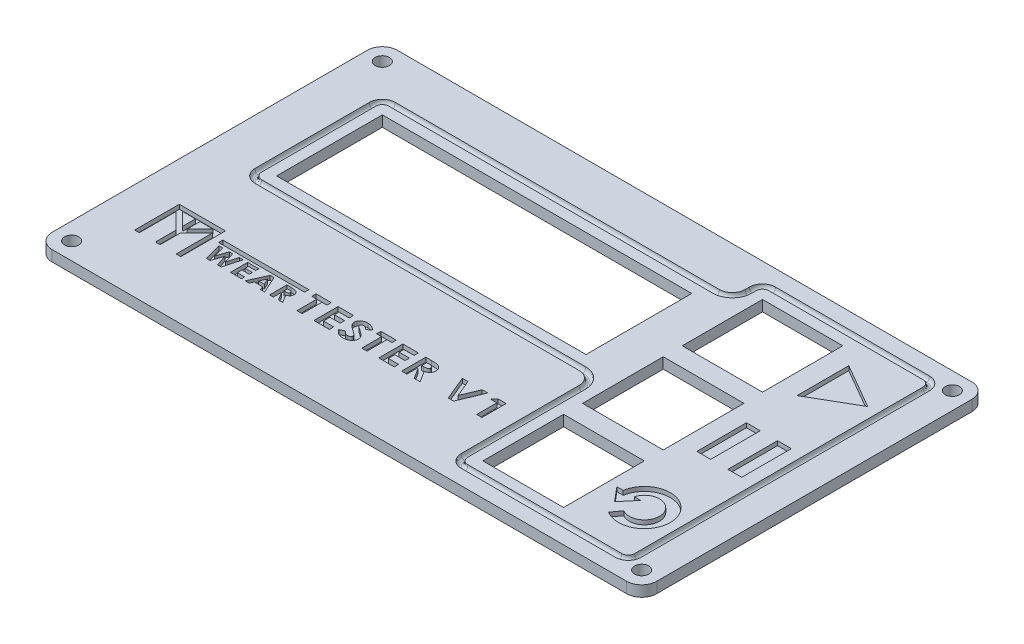
SolidWorks part; units mm, degrees
material "PET"
ref_plane "Front Plane" through (0, 0, 0) normal (0, 0, 1) x (1, 0, 0)
ref_plane "Top Plane" through (0, 0, 0) normal (0, 1, 0) x (1, 0, 0)
ref_plane "Right Plane" through (0, 0, 0) normal (1, 0, 0) x (0, 0, -1)
sketch "Sketch1" plane through (0, 0, 0) normal (0, 1, 0) x (1, 0, 0)
  line L0 (26.05, -9.1) -> (44.15, -9.1)
  line L1 (-55.05, 25) -> (16.05, 25) construction
  line L2 (-55.05, 25) -> (-55.05, 1.1) construction
  line L3 (-55.05, 1.1) -> (16.05, 1.1) construction
  line L4 (16.05, 25) -> (16.05, 1.1) construction
  line L5 (26.05, 14) -> (44.05, 14)
  line L6 (26.05, 14) -> (26.05, 32)
  line L7 (26.05, 32) -> (44.05, 32)
  line L8 (44.05, 14) -> (44.05, 32)
  line L9 (26.05, 14) -> (44.05, 32) construction
  line L10 (26.05, 32) -> (44.05, 14) construction
  line L11 (26.05, -9.1) -> (26.05, 9)
  line L12 (26.05, 9) -> (44.15, 9)
  line L13 (44.15, -9.1) -> (44.15, 9)
  line L14 (26.05, -9.1) -> (44.15, 9) construction
  line L15 (26.05, 9) -> (44.15, -9.1) construction
  line L16 (26.05, -32.2) -> (44.15, -32.2)
  line L17 (26.05, -32.2) -> (26.05, -14.1)
  line L18 (26.05, -14.1) -> (44.15, -14.1)
  line L19 (44.15, -32.2) -> (44.15, -14.1)
  line L20 (26.05, -32.2) -> (44.15, -14.1) construction
  line L21 (26.05, -14.1) -> (44.15, -32.2) construction
  line L22 (47.05, -9) -> (65.05, -9)
  line L23 (47.05, 14) -> (65.05, 14)
  line L24 (47.05, 14) -> (47.05, 32)
  line L25 (47.05, 32) -> (65.05, 32)
  line L26 (65.05, 14) -> (65.05, 32)
  line L27 (47.05, 14) -> (65.05, 32) construction
  line L28 (47.05, 32) -> (65.05, 14) construction
  line L29 (47.05, -9) -> (47.05, 9)
  line L30 (47.05, 9) -> (65.05, 9)
  line L31 (65.05, -9) -> (65.05, 9)
  line L32 (47.05, -9) -> (65.05, 9) construction
  line L33 (47.05, 9) -> (65.05, -9) construction
  line L34 (47.05, -32.1) -> (65.05, -32.1)
  line L35 (47.05, -32.1) -> (47.05, -14.1)
  line L36 (47.05, -14.1) -> (65.05, -14.1)
  line L37 (65.05, -32.1) -> (65.05, -14.1)
  line L38 (47.05, -32.1) -> (65.05, -14.1) construction
  line L39 (47.05, -14.1) -> (65.05, -32.1) construction
  line L40 (-55.35, 25.3) -> (16.35, 25.3)
  line L41 (-70.05, -40) -> (70.05, -40)
  line L42 (-70.05, -40) -> (-70.05, 40)
  line L43 (-70.05, 40) -> (70.05, 40)
  line L44 (70.05, -40) -> (70.05, 40)
  line L45 (-70.05, -40) -> (70.05, 40) construction
  line L46 (-70.05, 40) -> (70.05, -40) construction
  line L48 (-70.05, 0) -> (70.05, 0) construction
  line L50 (16.05, -25) -> (16.05, -1.1) construction
  line L51 (-55.05, -25) -> (16.05, -25) construction
  line L52 (-55.05, -25) -> (-55.05, -1.1) construction
  line L53 (-55.05, -1.1) -> (16.05, -1.1) construction
  line L55 (-59.45, 32.1) -> (20.55, 32.1) construction
  line L56 (-59.45, 32.1) -> (-59.45, -3.9) construction
  line L57 (-59.45, -3.9) -> (20.55, -3.9) construction
  line L58 (20.55, 32.1) -> (20.55, -3.9) construction
  line L60 (16.35, 25.3) -> (16.35, 0.8)
  line L61 (-55.35, 0.8) -> (16.35, 0.8)
  line L62 (-55.35, 25.3) -> (-55.35, 0.8)
  line L63 (25.75, 32.3) -> (44.35, 32.3)
  line L64 (44.35, 13.7) -> (44.35, 32.3)
  line L65 (25.75, 13.7) -> (44.35, 13.7)
  line L66 (25.75, 13.7) -> (25.75, 32.3)
  line L67 (25.75, 9.3) -> (44.45, 9.3)
  line L68 (44.45, -9.4) -> (44.45, 9.3)
  line L69 (25.75, -9.4) -> (44.45, -9.4)
  line L70 (25.75, -9.4) -> (25.75, 9.3)
  line L71 (25.75, -13.8) -> (44.45, -13.8)
  line L72 (44.45, -32.5) -> (44.45, -13.8)
  line L73 (25.75, -32.5) -> (44.45, -32.5)
  line L74 (25.75, -32.5) -> (25.75, -13.8)
  line L76 (-66.05, -36) -> (66.05, -36) construction
  line L77 (-66.05, -36) -> (-66.05, 36) construction
  line L78 (-66.05, 36) -> (66.05, 36) construction
  line L79 (66.05, -36) -> (66.05, 36) construction
  line L80 (-66.05, -36) -> (66.05, 36) construction
  line L81 (-66.05, 36) -> (66.05, -36) construction
  line L82 (-70.05, 40) -> (-85.05, 40)
  line L83 (-70.05, 40) -> (-70.05, -40)
  line L84 (-70.05, -40) -> (-85.05, -40)
  line L85 (-85.05, 40) -> (-85.05, -40)
  circle A0 centre (-66.05, 36) radius 1.65
  circle A1 centre (-66.05, -36) radius 1.65
  circle A2 centre (66.05, -36) radius 1.65
  circle A3 centre (66.05, 36) radius 1.65
  point P4 (35.05, 23)
  point P10 (35.1, -0.05)
  point P15 (35.1, -23.15)
  point P20 (56.05, 23)
  point P25 (56.05, 0)
  point P30 (56.05, -23.1)
  point P35 (0, 0)
  point P66 (0, 0)
  dimension "D25" = 3.3
  dimension "D1" = 71.1
  dimension "D2" = 23.9
  dimension "D3" = 18
  dimension "D4" = 18.1
  dimension "D5" = 18.1
  dimension "D6" = 18
  dimension "D7" = 18
  dimension "D8" = 18
  dimension "D9" = 5
  dimension "D10" = 5
  dimension "D11" = 3
  dimension "D12" = 8
  dimension "D13" = 80
  dimension "D15" = 10
  dimension "D16" = 15
  dimension "D17" = 15
  dimension "D18" = 5
  dimension "D19" = 36
  dimension "D20" = 80
  dimension "D21" = 5
  dimension "D22" = 4.5
  dimension "D26" = 4
  dimension "D24" = 4
  dimension "D27" = 15
  dimension "D14" = 0.3
  dimension "D23" = 0.3
extrude "Boss-Extrude1" add sketch "Sketch1" along normal blind 2.5 contours L41 L44 L43 L42 L69 L70 L67 L68 L37 L34 L35 L36 L31 L22 L29 L30 L26 L23 L24 L25 L62 L40 L60 L61 L65 L66 L63 L64 L73 L74 L71 L72 | L22 L31 L30 L29 | L23 L26 L25 L24 | L34 L37 L36 L35 region at (56.05, 0, 0) region at (56.05, 0, -23) region at (56.05, 0, 23.1) region at (-7.6894, 0, 3.0725)
fillet "Fillet1" radius 3.5 4 edges at (-70.05, 1.25, 40) (70.05, 1.25, 40) (70.05, 1.25, -40) (-70.05, 1.25, -40)
sketch "Sketch2" plane through (0, 2.5, 0) normal (0, 1, 0) x (1, 0, 0)
  line L0 (49.0427, 29) -> (49.0427, 17)
  line L1 (49.0427, 17) -> (59.435, 23)
  line L2 (59.435, 23) -> (49.0427, 29)
  line L3 (55.836, 5.7) -> (59.036, 5.7)
  line L4 (48.636, 5.7) -> (51.836, 5.7)
  line L5 (48.636, 5.7) -> (48.636, -5.8)
  line L6 (48.636, -5.8) -> (51.836, -5.8)
  line L7 (51.836, 5.7) -> (51.836, -5.8)
  line L8 (55.836, 5.7) -> (55.836, -5.8)
  line L9 (55.836, -5.8) -> (59.036, -5.8)
  line L10 (59.036, 5.7) -> (59.036, -5.8)
  line L11 (59.435, 23) -> (52.1492, 23) construction
  line L12 (59.036, -0.05) -> (48.636, -0.05) construction
  line L13 (53.836, 32.2951) -> (53.836, -34.6108) construction
  line L14 (49.2009, -25.4273) -> (46.4509, -22.15)
  line L15 (46.4509, -22.15) -> (47.9199, -22.15)
  line L16 (51.9509, -22.15) -> (49.2009, -25.4273)
  line L17 (57.0474, -22.15) -> (62.8011, -22.15) construction
  line L18 (50.4819, -22.15) -> (51.9509, -22.15)
  line L19 (50.6084, -28.2079) -> (52.085, -26.1805)
  line L20 (25.75, 23) -> (83.5755, 23) construction
  line L21 (25.75, 13.7) -> (25.75, 32.3) construction
  line L22 (25.75, -0.05) -> (86.018, -0.05) construction
  line L23 (25.75, -9.4) -> (25.75, 9.3) construction
  line L24 (25.75, -23.15) -> (93.8874, -23.15) construction
  line L25 (25.75, -32.5) -> (25.75, -13.8) construction
  line L26 (-63.1758, 72.6469) -> (86.8242, 72.6469) construction
  line L31 (-59.35, -0.2) -> (-59.35, 26.3)
  line L32 (-56.35, 29.3) -> (18.75, 29.3)
  line L33 (21.75, 32.3) -> (21.75, 33.3)
  line L34 (24.75, 36.3) -> (60.435, 36.3)
  line L35 (63.435, 33.3) -> (63.435, -33.5)
  line L36 (60.435, -36.5) -> (24.75, -36.5)
  line L37 (21.75, -33.5) -> (21.75, -6.2)
  line L38 (18.75, -3.2) -> (-56.35, -3.2)
  line L39 (-55.35, 25.3) -> (-55.35, 0.8) construction
  line L40 (-55.35, 0.8) -> (16.35, 0.8) construction
  line L41 (-55.5842, -5.7958) -> (-55.5842, -42.6703) construction
  line L42 (-55.35, 25.3) -> (16.35, 25.3) construction
  line L43 (25.75, 32.3) -> (44.35, 32.3) construction
  line L44 (25.75, -32.5) -> (44.45, -32.5) construction
  line L45 (-56.35, 27.8) -> (18.75, 27.8)
  line L46 (23.25, 32.3) -> (23.25, 33.3)
  line L47 (24.75, 34.8) -> (60.435, 34.8)
  line L48 (61.935, 33.3) -> (61.935, -33.5)
  line L49 (60.435, -35) -> (24.75, -35)
  line L50 (23.25, -33.5) -> (23.25, -6.2)
  line L51 (18.75, -1.7) -> (-56.35, -1.7)
  line L52 (-57.85, -0.2) -> (-57.85, 26.3)
  line L53 (-60.9283, -26.5177) -> (-60.9283, -16.1677)
  line L54 (-60.9283, -16.1677) -> (-50.24, -16.1677)
  line L55 (-60.9283, -26.5177) -> (-59.8499, -26.5177)
  line L56 (-59.8499, -26.5177) -> (-59.8499, -18.0492)
  line L57 (-59.8499, -18.0492) -> (-56.1242, -21.7607)
  line L58 (-56.1242, -21.7607) -> (-56.1242, -26.5177)
  line L59 (-56.1242, -26.5177) -> (-55.0442, -26.5177)
  line L60 (-59.1242, -17.2477) -> (-56.1242, -17.2477)
  line L61 (-56.1242, -17.2477) -> (-56.1242, -20.2363)
  line L62 (-56.1242, -20.2363) -> (-59.1242, -17.2477)
  line L63 (-55.0442, -20.2363) -> (-52.0442, -17.2477)
  line L64 (-55.0442, -17.2477) -> (-55.0442, -20.2363)
  line L65 (-52.0442, -17.2477) -> (-55.0442, -17.2477)
  line L66 (-55.0442, -21.7607) -> (-55.0442, -26.5177)
  line L67 (-51.3184, -18.0492) -> (-55.0442, -21.7607)
  line L68 (-51.3184, -26.5177) -> (-51.3184, -18.0492)
  line L69 (-50.24, -26.5177) -> (-51.3184, -26.5177)
  line L70 (-50.24, -26.5177) -> (-50.24, -16.1677)
  line L71 (-50.24, -16.1677) -> (15.8679, -16.1677) construction
  line L72 (-50.24, -26.5177) -> (17.2285, -26.5177) construction
  line L73 (-23.65, -6.2) -> (-23.65, -36) construction
  line L74 (-66.05, -6.2) -> (18.75, -6.2) construction
  line L75 (-66.05, -6.2) -> (-66.05, -36) construction
  line L76 (-66.05, -36) -> (18.75, -36) construction
  line L77 (18.75, -6.2) -> (18.75, -36) construction
  line L78 (-66.05, -21.1) -> (18.75, -21.1) construction
  line L79 (-48.2019, -23.9) -> (-29.2655, -23.9) construction
  line L80 (-48.7019, -18.3) -> (-28.7655, -18.3)
  line L81 (-48.7019, -18.3) -> (-48.7019, -19.3)
  line L82 (-48.7019, -19.3) -> (-28.7655, -19.3)
  line L83 (-28.7655, -18.3) -> (-28.7655, -19.3)
  line L84 (-48.2019, -18.3) -> (-29.2655, -18.3) construction
  line L85 (-27.241, -23.9) -> (18.0219, -23.9) construction
  line L86 (-48.0224, -19.9) -> (-47.1258, -19.9)
  line L87 (-47.1258, -19.9) -> (-46.4327, -22.4537)
  line L88 (-46.4327, -22.4537) -> (-45.5793, -19.9)
  line L89 (-45.5793, -19.9) -> (-44.8213, -19.9)
  line L90 (-44.8213, -19.9) -> (-43.9711, -22.4537)
  line L91 (-43.9711, -22.4537) -> (-43.2796, -19.9)
  line L92 (-43.2796, -19.9) -> (-42.3814, -19.9)
  line L93 (-42.3814, -19.9) -> (-43.4655, -23.9)
  line L94 (-43.4655, -23.9) -> (-44.3405, -23.9)
  line L95 (-44.3405, -23.9) -> (-45.2019, -21.3143)
  line L96 (-45.2019, -21.3143) -> (-46.0657, -23.9)
  line L97 (-46.0657, -23.9) -> (-46.9359, -23.9)
  line L98 (-46.9359, -23.9) -> (-48.0224, -19.9)
  line L99 (-41.3404, -19.9) -> (-38.7763, -19.9)
  line L100 (-38.7763, -19.9) -> (-38.7763, -20.6179)
  line L101 (-38.7763, -20.6179) -> (-40.4686, -20.6179)
  line L102 (-40.4686, -20.6179) -> (-40.4686, -21.3872)
  line L103 (-40.4686, -21.3872) -> (-38.7763, -21.3872)
  line L104 (-38.7763, -21.3872) -> (-38.7763, -22.1051)
  line L105 (-38.7763, -22.1051) -> (-40.4686, -22.1051)
  line L106 (-40.4686, -22.1051) -> (-40.4686, -23.1821)
  line L107 (-40.4686, -23.1821) -> (-38.7763, -23.1821)
  line L108 (-38.7763, -23.1821) -> (-38.7763, -23.9)
  line L109 (-38.7763, -23.9) -> (-41.3404, -23.9)
  line L110 (-41.3404, -23.9) -> (-41.3404, -19.9)
  line L111 (-36.1319, -19.9) -> (-35.2376, -19.9)
  line L112 (-35.2376, -19.9) -> (-33.4275, -23.9)
  line L113 (-33.4275, -23.9) -> (-34.3594, -23.9)
  line L114 (-34.3594, -23.9) -> (-34.7232, -23.0795)
  line L115 (-34.7232, -23.0795) -> (-36.6439, -23.0795)
  line L116 (-36.6439, -23.0795) -> (-37.0077, -23.9)
  line L117 (-37.0077, -23.9) -> (-37.9404, -23.9)
  line L118 (-37.9404, -23.9) -> (-36.1319, -19.9)
  line L119 (-35.6839, -20.9729) -> (-36.3266, -22.3615)
  line L120 (-36.3266, -22.3615) -> (-35.0413, -22.3615)
  line L121 (-35.0413, -22.3615) -> (-35.6839, -20.9729)
  line L122 (-32.2839, -19.9) -> (-31.3256, -19.9)
  line L123 (-30.3617, -22.0747) -> (-29.2327, -23.9)
  line L124 (-29.2327, -23.9) -> (-30.2158, -23.9)
  line L125 (-30.2158, -23.9) -> (-31.2944, -22.1564)
  line L126 (-31.2944, -22.1564) -> (-31.4121, -22.1564)
  line L127 (-31.4121, -22.1564) -> (-31.4121, -23.9)
  line L128 (-31.4121, -23.9) -> (-32.2839, -23.9)
  line L129 (-32.2839, -23.9) -> (-32.2839, -19.9)
  line L130 (-31.4121, -21.4385) -> (-31.1189, -21.4385)
  line L131 (-31.1557, -20.6179) -> (-31.4121, -20.6179)
  line L132 (-31.4121, -20.6179) -> (-31.4121, -21.4385)
  line L133 (-27.0974, -18.3) -> (-23.5794, -18.3)
  line L134 (-23.5794, -18.3) -> (-23.5794, -19.3051)
  line L135 (-23.5794, -19.3051) -> (-24.7281, -19.3051)
  line L136 (-24.7281, -19.3051) -> (-24.7281, -23.9)
  line L137 (-24.7281, -23.9) -> (-25.9487, -23.9)
  line L138 (-25.9487, -23.9) -> (-25.9487, -19.3051)
  line L139 (-25.9487, -19.3051) -> (-27.0974, -19.3051)
  line L140 (-27.0974, -19.3051) -> (-27.0974, -18.3)
  line L141 (-22.0143, -18.3) -> (-18.4246, -18.3)
  line L142 (-18.4246, -18.3) -> (-18.4246, -19.3051)
  line L143 (-18.4246, -19.3051) -> (-20.7938, -19.3051)
  line L144 (-20.7938, -19.3051) -> (-20.7938, -20.3821)
  line L145 (-20.7938, -20.3821) -> (-18.4246, -20.3821)
  line L146 (-18.4246, -20.3821) -> (-18.4246, -21.3872)
  line L147 (-18.4246, -21.3872) -> (-20.7938, -21.3872)
  line L148 (-20.7938, -21.3872) -> (-20.7938, -22.8949)
  line L149 (-20.7938, -22.8949) -> (-18.4246, -22.8949)
  line L150 (-18.4246, -22.8949) -> (-18.4246, -23.9)
  line L151 (-18.4246, -23.9) -> (-22.0143, -23.9)
  line L152 (-22.0143, -23.9) -> (-22.0143, -18.3)
  line L153 (-13.2697, -19.0482) -> (-14.2086, -19.7359)
  line L154 (-17.2902, -22.8511) -> (-16.2245, -22.3205)
  line L155 (-12.0635, -18.3) -> (-8.5456, -18.3)
  line L156 (-8.5456, -18.3) -> (-8.5456, -19.3051)
  line L157 (-8.5456, -19.3051) -> (-9.6943, -19.3051)
  line L158 (-9.6943, -19.3051) -> (-9.6943, -23.9)
  line L159 (-9.6943, -23.9) -> (-10.9148, -23.9)
  line L160 (-10.9148, -23.9) -> (-10.9148, -19.3051)
  line L161 (-10.9148, -19.3051) -> (-12.0635, -19.3051)
  line L162 (-12.0635, -19.3051) -> (-12.0635, -18.3)
  line L163 (-6.9804, -18.3) -> (-3.3907, -18.3)
  line L164 (-3.3907, -18.3) -> (-3.3907, -19.3051)
  line L165 (-3.3907, -19.3051) -> (-5.7599, -19.3051)
  line L166 (-5.7599, -19.3051) -> (-5.7599, -20.3821)
  line L167 (-5.7599, -20.3821) -> (-3.3907, -20.3821)
  line L168 (-3.3907, -20.3821) -> (-3.3907, -21.3872)
  line L169 (-3.3907, -21.3872) -> (-5.7599, -21.3872)
  line L170 (-5.7599, -21.3872) -> (-5.7599, -22.8949)
  line L171 (-5.7599, -22.8949) -> (-3.3907, -22.8949)
  line L172 (-3.3907, -22.8949) -> (-3.3907, -23.9)
  line L173 (-3.3907, -23.9) -> (-6.9804, -23.9)
  line L174 (-6.9804, -23.9) -> (-6.9804, -18.3)
  line L175 (-1.682, -18.3) -> (-0.3403, -18.3)
  line L176 (1.0092, -21.3446) -> (2.5898, -23.9)
  line L177 (2.5898, -23.9) -> (1.2134, -23.9)
  line L178 (1.2134, -23.9) -> (-0.2966, -21.459)
  line L179 (-0.2966, -21.459) -> (-0.4615, -21.459)
  line L180 (-0.4615, -21.459) -> (-0.4615, -23.9)
  line L181 (-0.4615, -23.9) -> (-1.682, -23.9)
  line L182 (-1.682, -23.9) -> (-1.682, -18.3)
  line L183 (-0.4615, -20.4538) -> (-0.0509, -20.4538)
  line L184 (-0.1025, -19.3051) -> (-0.4615, -19.3051)
  line L185 (-0.4615, -19.3051) -> (-0.4615, -20.4538)
  line L186 (6.797, -18.3) -> (8.0871, -18.3)
  line L187 (8.0871, -18.3) -> (9.7406, -22.2779)
  line L188 (9.7406, -22.2779) -> (11.3941, -18.3)
  line L189 (11.3941, -18.3) -> (12.6842, -18.3)
  line L190 (12.6842, -18.3) -> (10.3564, -23.9)
  line L191 (10.3564, -23.9) -> (9.1236, -23.9)
  line L192 (9.1236, -23.9) -> (6.797, -18.3)
  line L193 (15.0256, -18.3) -> (16.9416, -18.3)
  line L194 (16.9416, -18.3) -> (16.9416, -23.9)
  line L195 (16.9416, -23.9) -> (15.7211, -23.9)
  line L196 (15.7211, -23.9) -> (15.7211, -19.2333)
  line L197 (15.7211, -19.2333) -> (14.2852, -19.2333)
  line L198 (14.2852, -19.2333) -> (15.0256, -18.3)
  arc A0 (50.6084, -28.2079) -> (47.9199, -22.15) centre (53.836, -23.15) ccw
  arc A1 (52.085, -26.1805) -> (50.4819, -22.15) centre (53.836, -23.15) ccw
  arc A2 (51.287, -27.2761) -> (53.836, -18.3) centre (53.836, -23.15) ccw construction
  arc A3 (-59.35, 26.3) -> (-56.35, 29.3) centre (-56.35, 26.3) cw
  arc A4 (18.75, 29.3) -> (21.75, 32.3) centre (18.75, 32.3) ccw
  arc A5 (21.75, 33.3) -> (24.75, 36.3) centre (24.75, 33.3) cw
  arc A6 (60.435, 36.3) -> (63.435, 33.3) centre (60.435, 33.3) cw
  arc A7 (63.435, -33.5) -> (60.435, -36.5) centre (60.435, -33.5) cw
  arc A8 (24.75, -36.5) -> (21.75, -33.5) centre (24.75, -33.5) cw
  arc A9 (21.75, -6.2) -> (18.75, -3.2) centre (18.75, -6.2) ccw
  arc A10 (-59.35, -0.2) -> (-56.35, -3.2) centre (-56.35, -0.2) ccw
  arc A11 (18.75, 27.8) -> (23.25, 32.3) centre (18.75, 32.3) ccw
  arc A12 (23.25, 33.3) -> (24.75, 34.8) centre (24.75, 33.3) cw
  arc A13 (60.435, 34.8) -> (61.935, 33.3) centre (60.435, 33.3) cw
  arc A14 (61.935, -33.5) -> (60.435, -35) centre (60.435, -33.5) cw
  arc A15 (24.75, -35) -> (23.25, -33.5) centre (24.75, -33.5) cw
  arc A16 (23.25, -6.2) -> (18.75, -1.7) centre (18.75, -6.2) ccw
  arc A17 (-57.85, -0.2) -> (-56.35, -1.7) centre (-56.35, -0.2) ccw
  arc A18 (-57.85, 26.3) -> (-56.35, 27.8) centre (-56.35, 26.3) cw
  spline S0 degree 3 poles (-31.3256, -19.9) (-31.2038, -19.8994) (-31.0279, -19.9032) (-30.803, -19.9148) (-30.6554, -19.9274) (-30.5223, -19.9441) (-30.4034, -19.9641) (-30.2982, -19.9865) (-30.2057, -20.0144) (-30.1224, -20.0461) (-30.045, -20.0826) (-29.9713, -20.1231) (-29.9021, -20.1691) (-29.8369, -20.2197) (-29.7759, -20.2752) (-29.7188, -20.3355) (-29.6661, -20.4003) (-29.6181, -20.4685) (-29.5769, -20.5408) (-29.5418, -20.6158) (-29.5124, -20.6939) (-29.4913, -20.7754) (-29.4693, -20.8891) (-29.4634, -20.977) (-29.4634, -21.0362) knots 0 0 0 0 0.147269 0.212586 0.272219 0.326243 0.374706 0.418026 0.456127 0.491385 0.525617 0.55958 0.592893 0.626024 0.659167 0.692513 0.726248 0.760105 0.793224 0.826735 0.860141 0.893896 0.928408 1 1 1 1
  spline S1 degree 3 poles (-29.4634, -21.0362) (-29.4631, -21.0981) (-29.4694, -21.1896) (-29.4931, -21.3075) (-29.5184, -21.3904) (-29.5491, -21.4699) (-29.5883, -21.5451) (-29.6337, -21.6163) (-29.6866, -21.6834) (-29.7456, -21.7469) (-29.8131, -21.8054) (-29.8865, -21.861) (-29.9683, -21.9112) (-30.0563, -21.9584) (-30.1862, -22.0179) (-30.2901, -22.0532) (-30.3617, -22.0747) knots 0 0 0 0 0.124686 0.183969 0.241825 0.299057 0.355349 0.412196 0.4689 0.527122 0.586575 0.648431 0.712458 0.779597 0.849396 1 1 1 1
  spline S2 degree 3 poles (-31.1189, -21.4385) (-31.0503, -21.4375) (-30.9511, -21.4371) (-30.8254, -21.4257) (-30.7439, -21.4152) (-30.6711, -21.4034) (-30.6073, -21.386) (-30.5517, -21.3675) (-30.5043, -21.3448) (-30.4641, -21.3185) (-30.4292, -21.289) (-30.4002, -21.2546) (-30.3755, -21.217) (-30.3584, -21.1743) (-30.3391, -21.1117) (-30.335, -21.0609) (-30.3352, -21.0266) knots 0 0 0 0 0.204851 0.295232 0.376365 0.449979 0.515106 0.57331 0.624623 0.67125 0.716446 0.760519 0.804943 0.849927 0.897317 1 1 1 1
  spline S3 degree 3 poles (-30.3352, -21.0266) (-30.3341, -20.9848) (-30.3454, -20.9231) (-30.3802, -20.8477) (-30.4177, -20.7978) (-30.4628, -20.7524) (-30.516, -20.7141) (-30.5761, -20.6825) (-30.6319, -20.6624) (-30.683, -20.6499) (-30.729, -20.6412) (-30.7825, -20.6343) (-30.8429, -20.6278) (-30.9108, -20.6231) (-31.0157, -20.6187) (-31.0983, -20.6185) (-31.1557, -20.6179) knots 0 0 0 0 0.121157 0.179569 0.240198 0.301752 0.365181 0.430195 0.49879 0.537245 0.583128 0.6349 0.694296 0.75975 0.832876 1 1 1 1
  spline S4 degree 3 poles (-14.2086, -19.7359) (-14.2852, -19.6466) (-14.4043, -19.5229) (-14.578, -19.386) (-14.7039, -19.3044) (-14.8305, -19.2405) (-14.9986, -19.1805) (-15.1296, -19.1615) (-15.216, -19.1615) knots 0 0 0 0 0.295304 0.428877 0.553739 0.671168 0.78358 1 1 1 1
  spline S5 degree 3 poles (-15.216, -19.1615) (-15.2921, -19.1613) (-15.4038, -19.1723) (-15.5389, -19.2223) (-15.6238, -19.2711) (-15.6925, -19.3285) (-15.7605, -19.4077) (-15.7819, -19.4812) (-15.7825, -19.5284) knots 0 0 0 0 0.308989 0.447952 0.580945 0.703491 0.808979 1 1 1 1
  spline S6 degree 3 poles (-15.7825, -19.5284) (-15.7842, -19.5763) (-15.7584, -19.6739) (-15.7047, -19.759) (-15.6681, -19.7965) knots 0 0 0 0 0.475944 1 1 1 1
  spline S7 degree 3 poles (-15.6681, -19.7965) (-15.6323, -19.8357) (-15.5629, -19.895) (-15.4575, -19.9822) (-15.3492, -20.0659) (-15.2227, -20.1629) (-15.0132, -20.3144) (-14.8482, -20.4367) (-14.7291, -20.5189) knots 0 0 0 0 0.133977 0.23076 0.34601 0.48035 0.633996 1 1 1 1
  spline S8 degree 3 poles (-14.7291, -20.5189) (-14.6195, -20.5968) (-14.4622, -20.7052) (-14.2673, -20.8462) (-14.1458, -20.931) (-14.045, -21.0074) (-13.9437, -21.0819) (-13.8782, -21.134) (-13.8407, -21.1651) knots 0 0 0 0 0.367089 0.521493 0.656908 0.771457 0.867017 1 1 1 1
  spline S9 degree 3 poles (-13.8407, -21.1651) (-13.7229, -21.2649) (-13.5612, -21.4162) (-13.3847, -21.6348) (-13.2869, -21.7894) (-13.2155, -21.9464) (-13.1439, -22.1628) (-13.1268, -22.3347) (-13.1261, -22.4495) knots 0 0 0 0 0.304367 0.434332 0.552442 0.663491 0.773417 1 1 1 1
  spline S10 degree 3 poles (-13.1261, -22.4495) (-13.1272, -22.5603) (-13.1411, -22.7261) (-13.2029, -22.9351) (-13.2633, -23.0834) (-13.3444, -23.2226) (-13.4406, -23.356) (-13.5569, -23.4798) (-13.6883, -23.5956) (-13.8341, -23.7008) (-13.9916, -23.7933) (-14.1602, -23.8704) (-14.3393, -23.9338) (-14.529, -23.9825) (-14.8021, -24.0318) (-15.0145, -24.0437) (-15.1588, -24.0436) knots 0 0 0 0 0.11537 0.171176 0.225852 0.28135 0.338062 0.396328 0.45742 0.51973 0.582747 0.646876 0.711984 0.779813 0.850057 1 1 1 1
  spline S11 degree 3 poles (-15.1588, -24.0436) (-15.273, -24.0436) (-15.4421, -24.0353) (-15.6625, -24.005) (-15.8199, -23.9737) (-15.9717, -23.9333) (-16.1176, -23.8842) (-16.2575, -23.8251) (-16.3926, -23.7583) (-16.5221, -23.6801) (-16.6468, -23.5928) (-16.766, -23.4944) (-16.8811, -23.3865) (-16.9903, -23.2672) (-17.1343, -23.0935) (-17.2303, -22.9508) (-17.2902, -22.8511) knots 0 0 0 0 0.133395 0.197302 0.259636 0.320637 0.380558 0.439264 0.49784 0.556394 0.615625 0.675497 0.736652 0.79968 0.864191 1 1 1 1
  spline S12 degree 3 poles (-16.2245, -22.3205) (-16.1506, -22.4323) (-16.03, -22.5855) (-15.8481, -22.7582) (-15.7115, -22.8608) (-15.5695, -22.9398) (-15.3748, -23.0161) (-15.22, -23.0384) (-15.1173, -23.0385) knots 0 0 0 0 0.292061 0.422952 0.545866 0.663349 0.776115 1 1 1 1
  spline S13 degree 3 poles (-15.1173, -23.0385) (-15.0159, -23.039) (-14.8676, -23.0205) (-14.6851, -22.953) (-14.5694, -22.8824) (-14.4716, -22.8015) (-14.3777, -22.6834) (-14.345, -22.5776) (-14.3466, -22.5079) knots 0 0 0 0 0.29547 0.430685 0.56414 0.688619 0.798928 1 1 1 1
  spline S14 degree 3 poles (-14.3466, -22.5079) (-14.345, -22.4416) (-14.372, -22.3414) (-14.4416, -22.2168) (-14.5036, -22.1381) (-14.567, -22.072) (-14.6291, -22.0155) (-14.703, -21.9511) (-14.791, -21.8822) (-14.8908, -21.806) (-15.0478, -21.6893) (-15.1751, -21.6031) (-15.2631, -21.542) knots 0 0 0 0 0.142846 0.221999 0.309697 0.360419 0.421544 0.492612 0.573811 0.665086 0.766465 1 1 1 1
  spline S15 degree 3 poles (-15.2631, -21.542) (-15.4316, -21.4271) (-15.6719, -21.259) (-15.9716, -21.0355) (-16.1613, -20.8854) (-16.3265, -20.7462) (-16.4687, -20.619) (-16.5857, -20.5015) (-16.6808, -20.3925) (-16.7569, -20.288) (-16.8232, -20.1867) (-16.8778, -20.0848) (-16.9232, -19.9828) (-16.9596, -19.8814) (-16.9918, -19.7465) (-17.0045, -19.6446) (-17.003, -19.5766) knots 0 0 0 0 0.224706 0.322998 0.411848 0.491073 0.561071 0.621952 0.67365 0.720203 0.764311 0.806888 0.84746 0.887198 0.925366 1 1 1 1
  spline S16 degree 3 poles (-17.003, -19.5766) (-17.0035, -19.4819) (-16.9877, -19.3403) (-16.9315, -19.1605) (-16.8738, -19.0317) (-16.8002, -18.9079) (-16.7086, -18.7904) (-16.6013, -18.6779) (-16.4796, -18.5721) (-16.3457, -18.475) (-16.2022, -18.3898) (-16.0508, -18.3177) (-15.8922, -18.2579) (-15.7258, -18.2122) (-15.4899, -18.1677) (-15.3071, -18.1573) (-15.1835, -18.1564) knots 0 0 0 0 0.110922 0.165527 0.22025 0.275859 0.333966 0.394405 0.45776 0.522707 0.587935 0.653004 0.719007 0.7863 0.854965 1 1 1 1
  spline S17 degree 3 poles (-15.1835, -18.1564) (-15.0213, -18.1567) (-14.779, -18.1803) (-14.4658, -18.2602) (-14.276, -18.3309) (-14.1253, -18.4007) (-14.0096, -18.4638) (-13.892, -18.5375) (-13.7703, -18.6186) (-13.6487, -18.7127) (-13.4778, -18.8526) (-13.3522, -18.9667) (-13.2697, -19.0482) knots 0 0 0 0 0.224009 0.334383 0.445685 0.503229 0.563788 0.627577 0.694912 0.765681 0.839823 1 1 1 1
  spline S18 degree 3 poles (-0.3403, -18.3) (-0.1697, -18.2992) (0.0764, -18.3045) (0.3913, -18.3208) (0.5979, -18.3384) (0.7843, -18.3618) (0.9508, -18.3897) (1.0981, -18.4211) (1.2276, -18.4602) (1.3441, -18.5045) (1.4526, -18.5557) (1.5557, -18.6123) (1.6526, -18.6768) (1.7438, -18.7476) (1.8293, -18.8252) (1.9092, -18.9096) (1.9829, -19.0004) (2.0502, -19.0959) (2.1079, -19.1971) (2.157, -19.3022) (2.1982, -19.4115) (2.2277, -19.5256) (2.2586, -19.6847) (2.2667, -19.8078) (2.2667, -19.8907) knots 0 0 0 0 0.147269 0.212586 0.272219 0.326243 0.374706 0.418026 0.456127 0.491385 0.525617 0.55958 0.592893 0.626024 0.659167 0.692513 0.726248 0.760105 0.793224 0.826735 0.860141 0.893896 0.928408 1 1 1 1
  spline S19 degree 3 poles (2.2667, -19.8907) (2.2671, -19.9774) (2.2583, -20.1054) (2.2252, -20.2705) (2.1897, -20.3866) (2.1467, -20.4979) (2.0919, -20.6031) (2.0283, -20.7028) (1.9543, -20.7967) (1.8717, -20.8857) (1.7772, -20.9675) (1.6744, -21.0454) (1.5599, -21.1157) (1.4368, -21.1818) (1.2548, -21.2651) (1.1094, -21.3145) (1.0092, -21.3446) knots 0 0 0 0 0.124686 0.183969 0.241825 0.299057 0.355349 0.412196 0.4689 0.527122 0.586575 0.648431 0.712458 0.779597 0.849396 1 1 1 1
  spline S20 degree 3 poles (-0.0509, -20.4538) (0.0452, -20.4525) (0.1839, -20.452) (0.3599, -20.436) (0.474, -20.4213) (0.576, -20.4048) (0.6653, -20.3804) (0.7432, -20.3545) (0.8095, -20.3228) (0.8659, -20.2859) (0.9147, -20.2446) (0.9553, -20.1965) (0.9899, -20.1438) (1.0138, -20.084) (1.0408, -19.9964) (1.0465, -19.9253) (1.0462, -19.8772) knots 0 0 0 0 0.204851 0.295232 0.376365 0.449979 0.515106 0.57331 0.624623 0.67125 0.716446 0.760519 0.804943 0.849927 0.897317 1 1 1 1
  spline S21 degree 3 poles (1.0462, -19.8772) (1.0478, -19.8187) (1.032, -19.7324) (0.9832, -19.6268) (0.9308, -19.557) (0.8677, -19.4934) (0.7932, -19.4397) (0.709, -19.3955) (0.6308, -19.3674) (0.5593, -19.3498) (0.495, -19.3377) (0.42, -19.328) (0.3355, -19.3189) (0.2405, -19.3123) (0.0935, -19.3062) (-0.0221, -19.3059) (-0.1025, -19.3051) knots 0 0 0 0 0.121157 0.179569 0.240198 0.301752 0.365181 0.430195 0.49879 0.537245 0.583128 0.6349 0.694296 0.75975 0.832876 1 1 1 1
  point P16 (55.7921, 23)
  point P17 (53.836, -0.05)
  point P27 (49.4767, -21.0243)
  point P68 (21.75, 29.3)
  point P108 (-55.5842, -26.5177)
  point P126 (-55.5842, -16.1677)
  dimension "D8" = 2.5
  dimension "D9" = 1.35
  dimension "D11" = 12
  dimension "D21" = 3
  dimension "D22" = 3
  dimension "D1" = 60
  dimension "D2" = 60
  dimension "D3" = 4
  dimension "D4" = 3.2
  dimension "D5" = 3.2
  dimension "D6" = 12
  dimension "D7" = 11.5
  dimension "D10" = 50
  dimension "D12" = 1
  dimension "D13" = 5.5
  dimension "D14" = 4
  dimension "D15" = 4
  dimension "D16" = 4
  dimension "D17" = 4
  dimension "D18" = 4
  dimension "D19" = 4
  dimension "D20" = 4
  dimension "D24" = 1.0784
  dimension "D25" = 10.35
  dimension "D26" = 5.3441
  dimension "D27" = 1.08
  dimension "D28" = 1.08
  dimension "D29" = 1.08
  dimension "D30" = 2.8
  dimension "D31" = 1
  dimension "D32" = 3
  dimension "D33" = 0.5
  dimension "D34" = 0.5
  dimension "D23" = 1.5
extrude "Cut-Extrude2" cut sketch "Sketch2" against normal blind 1 contours L69 L70 L54 L53 L55 L56 L57 L58 L59 L66 L67 L68 L61 L62 L60 L65 L63 L64 | L98 L97 L96 L95 L94 L93 L92 L91 L90 L89 L88 L87 L86 | L83 L80 L81 L82 | L118 L117 L116 L115 L114 L113 L112 L111 L121 L120 L119 | L110 L109 L108 L107 L106 L105 L104 L103 L102 L101 L100 L99 | S1 S0 L122 L129 L128 L127 L126 L125 L124 L123 S3 S2 L130 L132 L131 | L140 L139 L138 L137 L136 L135 L134 L133 | L152 L151 L150 L149 L148 L147 L146 L145 L144 L143 L142 L141 | S17 S16 S15 S14 S13 S12 L154 S11 S10 S9 S8 S7 S6 S5 S4 L153 | L162 L161 L160 L159 L158 L157 L156 L155 | L174 L173 L172 L171 L170 L169 L168 L167 L166 L165 L164 L163 | S19 S18 L175 L182 L181 L180 L179 L178 L177 L176 S21 S20 L183 L185 L184 | L192 L191 L190 L189 L188 L187 L186 | L198 L197 L196 L195 L194 L193 | A1 L19 A0 L15 L14 L16 L18 | L7 L4 L5 L6 | L10 L3 L8 L9 | L1 L2 L0 | L31 A10 L38 A9 L37 A8 L36 A7 L35 A6 L34 A5 L33 A4 L32 A3 L52 A18 L45 A11 L46 A12 L47 A13 L48 A14 L49 A15 L50 A16 L51 A17 region at (52.5068, 2.5, -23) region at (57.436, 2.5, 0.05) region at (50.236, 2.5, 0.05) region at (47.9636, 2.5, 23.6731) region at (-57.9226, 2.5, -13.05) region at (-55.5842, 2.5, 20.197) region at (-38.7337, 2.5, 18.8) region at (-47.5741, 2.5, 19.9692) region at (-40.2492, 2.5, 21.8738) region at (-35.6847, 2.5, 19.9603) region at (-31.0065, 2.5, 21.8206) region at (-25.3384, 2.5, 20.5198) region at (-20.4867, 2.5, 21.0633) region at (-15.1198, 2.5, 21.1716) region at (-10.3046, 2.5, 20.5198) region at (-5.4529, 2.5, 21.0633) region at (0.1064, 2.5, 20.9888) region at (7.442, 2.5, 18.3813) region at (16.1834, 2.5, 20.8104)
fillet "Fillet2" radius 0.6 16 edges at (42.5925, 1.5, 36.5) (22.6287, 1.5, 35.6213) (62.5563, 1.5, 35.6213) (21.75, 1.5, 19.85) (63.435, 1.5, 0.1) (20.8713, 1.5, 4.0787) (62.5563, 1.5, -35.4213) (-18.8, 1.5, 3.2) (42.5925, 1.5, -36.3) (-58.4713, 1.5, 2.3213) (22.6287, 1.5, -35.4213) (-59.35, 1.5, -13.05) (21.75, 1.5, -32.8) (-58.4713, 1.5, -28.4213) (20.8713, 1.5, -30.1787) (-18.8, 1.5, -29.3) second distance 1 first distance on face at (11.8963, 1.5, -6.475)
fillet "Fillet3" radius 1 16 edges at (42.5925, 1.5, 35) (23.6893, 1.5, 34.5607) (61.4957, 1.5, 34.5607) (23.25, 1.5, 19.85) (61.935, 1.5, 0.1) (21.932, 1.5, 3.018) (61.4957, 1.5, -34.3607) (-18.8, 1.5, 1.7) (42.5925, 1.5, -34.8) (-57.4107, 1.5, 1.2607) (23.6893, 1.5, -34.3607) (-57.85, 1.5, -13.05) (23.25, 1.5, -32.8) (-57.4107, 1.5, -27.3607) (21.932, 1.5, -29.118) (-18.8, 1.5, -27.8) second distance 0.6 first distance on face at (42.5925, 2, 35) first distance on face at (23.8447, 2, 34.4053) first distance on face at (61.3404, 2, 34.4053) first distance on face at (23.25, 2, 19.85) first distance on face at (61.935, 2, 0.1) first distance on face at (21.466, 2, 3.484) first distance on face at (61.3404, 2, -34.2053) first distance on face at (-18.8, 2, 1.7) first distance on face at (42.5925, 2, -34.8) first distance on face at (-57.2553, 2, 1.1053) first distance on face at (23.8447, 2, -34.2053) first distance on face at (-57.85, 2, -13.05) first distance on face at (23.25, 2, -32.8) first distance on face at (-57.2553, 2, -27.2053) first distance on face at (21.466, 2, -29.584) first distance on face at (-18.8, 2, -27.8)
equation "\"width\"= 80"
equation "\"D13@Sketch1\"=\"width\""
